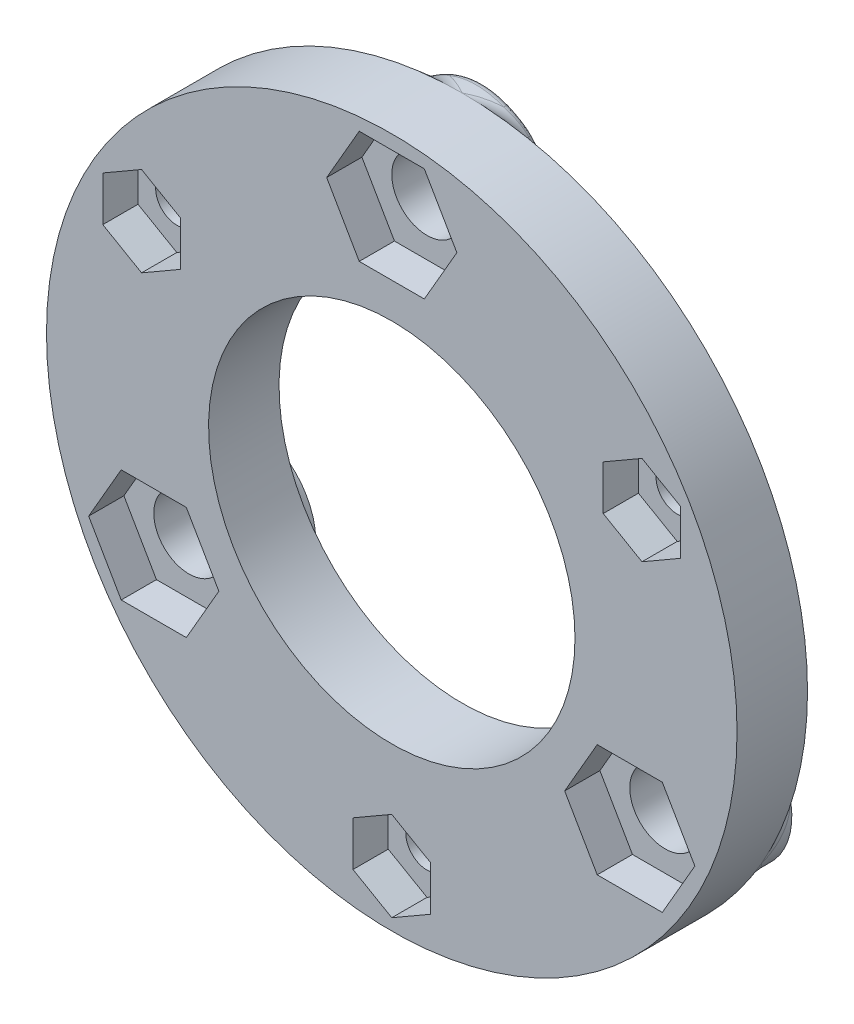
SolidWorks part; units mm, degrees
ref_plane "Front Plane" through (0, 0, 0) normal (0, 0, 1) x (1, 0, 0)
ref_plane "Top Plane" through (0, 0, 0) normal (0, 1, 0) x (1, 0, 0)
ref_plane "Right Plane" through (0, 0, 0) normal (1, 0, 0) x (0, 0, -1)
sketch "Sketch2" plane through (0, 0, 0) normal (0, 0, 1) x (1, 0, 0)
  line L0 (0, 19.5) -> (0, 0) construction
  line L1 (0, 0) -> (17.7535, 10.25) construction
  circle A0 centre (0, 0) radius 24.5
  circle A1 centre (0, 0) radius 13
  circle A2 centre (0, 0) radius 19.5 construction
  circle A3 centre (0, 19.5) radius 2.5
  circle A4 centre (0, 0) radius 20.5 construction
  circle A5 centre (16.8875, -9.75) radius 2.5
  circle A8 centre (17.7535, 10.25) radius 1.5
  circle A9 centre (0, -20.5) radius 1.5
  circle A11 centre (0, 0) radius 6.5 construction
  circle A14 centre (0, 19.5) radius 5 construction
  circle A15 centre (0, 0) radius 14.5 construction
  circle A16 centre (-16.8875, -9.75) radius 2.5
  circle A19 centre (-17.7535, 10.25) radius 1.5
  point P17 (0, 0)
  point P24 (0, 0)
  dimension "D1" = 49
  dimension "D2" = 39
  dimension "D4" = 5
  dimension "D7" = 3
  dimension "D3" = 13
  dimension "D10" = 10
  dimension "D5" = 4
  dimension "D9" = 1.5
  dimension "D11" = 60
  dimension "D6" = 3
  dimension "D8" = 3
extrude "Boss-Extrude1" add sketch "Sketch2" along normal blind 5
sketch "Sketch3" plane through (0, 0, 5) normal (0, 0, 1) x (1, 0, 0)
  line L0 (0, 19.5) -> (0, 0) construction
  line L13 (-4.6188, 19.5) -> (-2.3094, 15.5)
  line L14 (-2.3094, 15.5) -> (2.3094, 15.5)
  line L15 (2.3094, 15.5) -> (4.6188, 19.5)
  line L16 (4.6188, 19.5) -> (2.3094, 23.5)
  line L17 (2.3094, 23.5) -> (-2.3094, 23.5)
  line L18 (-2.3094, 23.5) -> (-4.6188, 19.5)
  line L20 (17.7535, 7.0746) -> (20.5035, 8.6623)
  line L21 (20.5035, 8.6623) -> (20.5035, 11.8377)
  line L22 (20.5035, 11.8377) -> (17.7535, 13.4254)
  line L23 (17.7535, 13.4254) -> (15.0035, 11.8377)
  line L24 (15.0035, 11.8377) -> (15.0035, 8.6623)
  line L25 (15.0035, 8.6623) -> (17.7535, 7.0746)
  circle A0 centre (0, 19.5) radius 4 construction
  circle A1 centre (17.7535, 10.25) radius 2.75 construction
  dimension "D1" = 8
  dimension "D2" = 5.5
extrude "Cut-Extrude1" cut sketch "Sketch3" against normal blind 2.5
pattern_circular "CirPattern1" count 3 over 360 about axis through (0, 0, 5) along (0, 0, -1) of "Cut-Extrude1" reverse direction yes
sketch "Sketch4" plane through (0, 0, 0) normal (0, 0, -1) x (-1, 0, 0)
  circle A0 centre (0, 19.5) radius 4
  circle A1 centre (0, 19.5) radius 5
  dimension "D1" = 8
extrude "Boss-Extrude2" add sketch "Sketch4" along normal blind 1.5
fillet "Fillet1" radius 1.5 1 edges at (-5, 19.5, 0)
fillet "Fillet2" radius 0.5 2 edges at (0, 24.5, -1.5) (0, 14.5, -1.5)
chamfer "Chamfer1" distance 0.25 angle 45 1 edges at (-4, 19.5, -1.5)
pattern_circular "CirPattern2" count 3 over 360 about axis through (0, 0, 5) along (0, 0, -1) of "Fillet1", "Boss-Extrude2", "Chamfer1" reverse direction yes
equation "\"Nr\"= \"Ns\" + 2 * \"Np\"'num teeth"
equation "\"module\"= 0.65"
equation "\"pressure_angle\"= 20deg"
equation "\"h_a\"= 1 * \"module\"'addendum"
equation "\"h_f\"= 1.25 * \"module\"'dedendum"
equation "\"clr_tip_root\"= \"h_f\" - \"h_a\"'clearance of gear tooth tip and root"
equation "\"dp_r\"= \"module\" * \"Nr\"'PCD"
equation "\"db_r\"= \"dp_r\" * cos ( \"pressure_angle\" )'base CD"
equation "\"fw_r\"= 11.5mm'face width"
equation "\"alpha_r\"= sqr ( \"dp_r\" ^ 2 - \"db_r\" ^ 2 ) / \"db_r\" * 180 / pi - \"pressure_angle\""
equation "\"beta_r\"= ( 360 / ( 4 * \"Nr\" ) + \"alpha_r\" ) * 2"
equation "\"bearing_ID\"= \"module\" * ( \"Ns\" + \"Np\" ) + 10"
equation "\"bearing_OD\"= 1.18 * \"bearing_ID\" + 8.57"
equation "\"bearing_height\"= 0.09 * \"bearing_ID\" + 4.62"
equation "\"clearance_planet\"=1.5"
equation "\"case_dist\"= \"sec_carrier_thickness\" + \"clearance_planet\" + \"sun_coupler_hub_thickness\" - \"case_mounting_surface_height\""
equation "\"Motor_case_OD_max\"= \"case_mounting_PCD\" + \"case_mounting_hole_allen_socket_dia\" + \"clearance_case_mount_holes_shell_thickness\" * 2"
equation "\"case_mounting_PCD\"= \"motor_case_OD_base\" + \"case_mounting_hole_shift\" * 2"
equation "\"bearing mount thickness\"= \"output_mounting_hole_dia\" * 2"
equation "\"case_mounting_hole_dia\"=3"
equation "\"output_mounting_PCD\"= \"bearing_OD\" + \"bearing mount thickness\""
equation "\"output_mounting_hole_dia\"= 4"
equation "\"clearance_case_mount_holes_shell_thickness\"= 1"
equation "\"motor_case_OD_base\"= \"motor_OD\" + \"clearance_motor_and_case\" * 2 + \"Motor_case_thickness\" * 2"
equation "\"sec_carrier_thickness\"= 5"
equation "\"sun_coupler_hub_thickness\"= 4"
equation "\"clearance_sun_coupler_sec_carrier\"= 1.5"
equation "\"clearance_motor_and_case\"= 2.2"
equation "\"motor_OD\"= 72"
equation "\"Motor_case_thickness\"= 2"
equation "\"Motor_case_ID\"= \"motor_OD\" + \"clearance_motor_and_case\" * 2"
equation "\"case_mounting_hole_shift\"= \"case_mounting_hole_dia\" / 2 - 0.5"
equation "\"output_mounting_nut_wrench_size\"= 7"
equation "\"output_mounting_nut_thickness\"= 3.2"
equation "\"case_mounting_hole_allen_socket_dia\"= 5.5"
equation "\"output_mounting_nut_depth\"= 3"
equation "\"case_mounting_bolt_depth\"= 4.5"
equation "\"Ns\"= 20"
equation "\"Np\"= 40"
equation "\"ring_radial_thickness\"= 5"
equation "\"ring_OD\"= \"Nr\" * \"module\" + \"ring_radial_thickness\" * 2"
equation "\"ring_to_chamfer_clearance\"= 2"
equation "\"Motor_case_OD_base_to_chamfer\"=5"
equation "\"pattern_offset_from_motor_case_OD_base\"= 3"
equation "\"pattern_bulge_dia\"= 3"
equation "\"pattern_num_bulge\"= 18"
equation "\"pattern_depth\"= 2"
equation "\"motor_height\"= 27"
equation "\"case_mounting_wrench_size\"= 5.5"
equation "\"case_mounting_nut_clearance\"= 2"
equation "\"base_plate_thickness\"= 4"
equation "\"case_mounting_nut_thickness\"= 2.4"
equation "\"case_mounting_surface_height\"= 4"
equation "\"motor_mount_hole_PCD\"= 32"
equation "\"motor_mount_hole_dia\"= 4"
equation "\"motor_mount_hole_num\"= 4"
equation "\"central_hole_offset_from_motor_mount_PCD\"= 5"
equation "\"wire_slot_dist_from_center\"= 30"
equation "\"wire_slot_length\"= 10"
equation "\"wire_slot_radius\"= 4"
equation "\"driver_upper_holes_dist_from_center\"= 23"
equation "\"driver_lower_holes_dist_from_center\"= 15"
equation "\"driver_side_holes_dist_from_center\"= 20"
equation "\"driver_mount_holes_dia\"= 2.5"
equation "\"driver_mount_inserts_OD\"= 3.5"
equation "\"driver_mount_thickness\"= 1.5"
equation "\"driver_mount_height\"= 4"
equation "\"air_flow_hole_offset\"= 3"
equation "\"num_planet\"= 3"
equation "\"planet_pin_bolt_dia\"= 5"
equation "\"planet_pin_socket_head_dia\"= 8.5"
equation "\"carrier_PCD\"= ( \"Np\" + \"Ns\" ) * \"module\""
equation "\"D1@Sketch2\"=\"bearing_ID\""
equation "\"D2@Sketch2\"=\"carrier_PCD\""
equation "\"D4@Sketch2\"=\"planet_pin_bolt_dia\""
equation "\"D6@Sketch2\"=\"num_planet\""
equation "\"D8@Sketch2\"=\"num_planet\""
equation "\"D1@CirPattern1\"=\"num_planet\""
equation "\"planet_shaft_dia\"= 8"
equation "\"fw_p\"= \"fw_r\""
equation "\"planet_shaft_step_offset\"= 1"
equation "\"carrier_trapezoidal_support_sun_offset\"= 5"
equation "\"carrier_trapezoidal_support_hole_PCD_offset_bearing_ID\"= 4"
equation "\"carrier_trapezoidal_support_hole_dia\"= 3"
equation "\"carrier_trapezoidal_support_hole_socket_head_dia\"= 5.5"
equation "\"carrier_bearing_step_width\"= 1.5"
equation "\"standard_clearance_1_5mm\"=1.5"
equation "\"standard_fillet_1_5mm\"= 1.5"
equation "\"sun_shaft_bearing_OD\"= 16"
equation "\"sun_shaft_bearing_width\"= 4"
equation "\"standard_bearing_insertion_chamfer\"= 0.5"
equation "\"D7@Sketch2\"=\"carrier_trapezoidal_support_hole_dia\""
equation "\"D5@Sketch2\"=\"carrier_trapezoidal_support_hole_PCD_offset_bearing_ID\""
equation "\"D3@Sketch2\"=\"Ns\"*\"module\""
equation "\"carrier_trapezoidal_support_hole_wrench_size\"= 5.5"
equation "\"planet_pin_bolt_wrench_size\"= 8"
equation "\"D1@Boss-Extrude1\"=\"sec_carrier_thickness\""
equation "\"D1@Cut-Extrude1\"=\"sec_carrier_thickness\"/2"
equation "\"D1@Sketch4\"=\"planet_shaft_dia\""
equation "\"D2@Sketch4\"=\"planet_shaft_step_offset\""
equation "\"D1@Boss-Extrude2\"=\"clearance_planet\""
equation "\"D1@Fillet1\"=\"standard_fillet_1_5mm\""
equation "\"D1@Chamfer1\"=\"standard_bearing_insertion_chamfer\"/2"
equation "\"D1@Fillet2\"=\"standard_fillet_1_5mm\"/3"
equation "\"D1@CirPattern2\"=\"num_planet\""
equation "\"D10@Sketch2\"=\"planet_shaft_dia\"+\"planet_shaft_step_offset\"*2"
equation "\"D9@Sketch2\"=\"standard_clearance_1_5mm\""
equation "\"D1@Sketch3\"=\"planet_pin_bolt_wrench_size\""
equation "\"D11@Sketch2\"=180/\"num_planet\""
equation "\"D2@Sketch3\"=\"carrier_trapezoidal_support_hole_wrench_size\""
